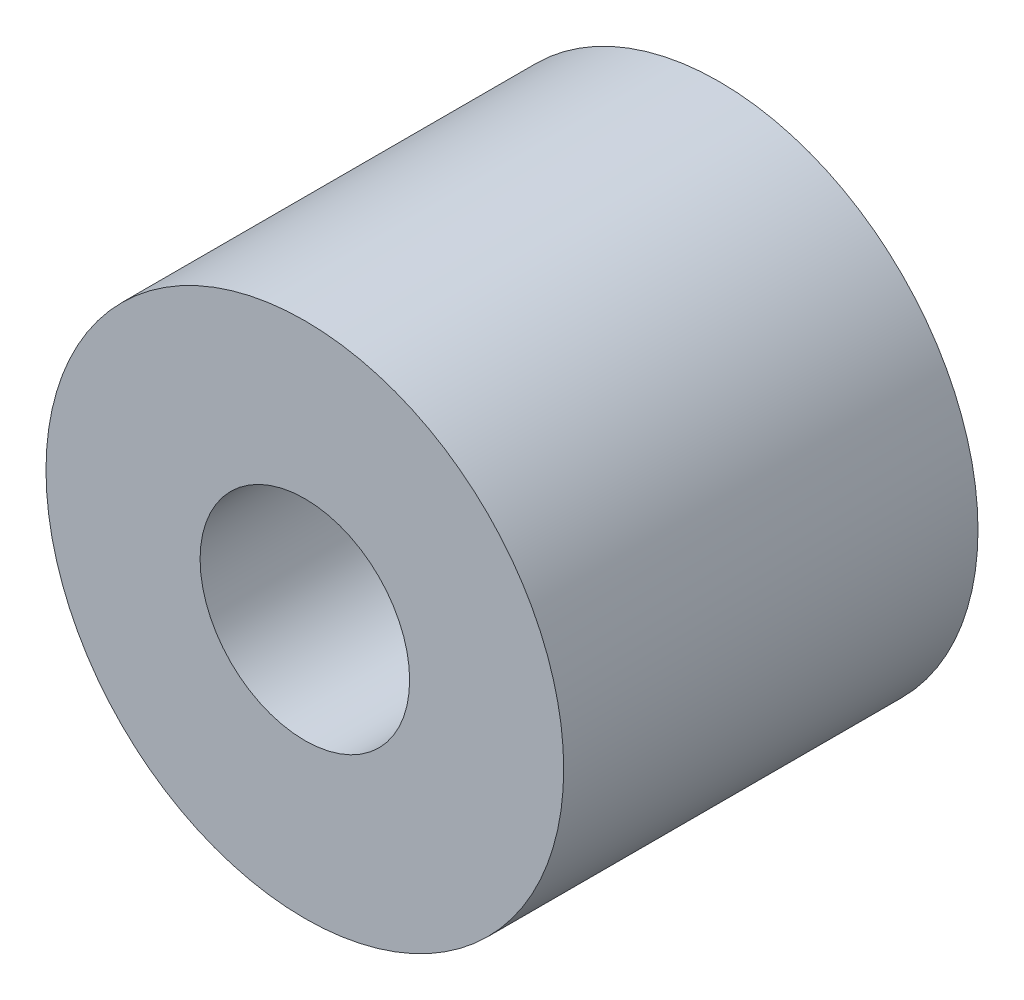
SolidWorks part; units mm, degrees
ref_plane "Front Plane" through (0, 0, 0) normal (0, 0, 1) x (1, 0, 0)
ref_plane "Top Plane" through (0, 0, 0) normal (0, 1, 0) x (1, 0, 0)
ref_plane "Right Plane" through (0, 0, 0) normal (1, 0, 0) x (0, 0, -1)
sketch "Sketch1" plane through (0, 0, 0) normal (0, 1, 0) x (1, 0, 0)
  line L0 (2.125, -3.75) -> (5.25, -3.75)
  line L1 (5.25, -3.75) -> (5.25, 0)
  line L2 (5.25, 0) -> (2.125, 0)
  line L3 (2.125, 0) -> (2.125, -3.75)
  line L4 (0, 0) -> (0, -3.75) construction
  dimension "D1" = 2.125
  dimension "D2" = 5.25
  dimension "D3" = 3.75
revolve "Revolve1" add sketch "Sketch1" angle 360 about L4 reverse direction yes
sketch "Sketch2" plane through (0, 0, 3.75) normal (0, 0, 1) x (1, 0, 0)
  circle A0 centre (0, 0) radius 2.125
  circle A1 centre (0, 0) radius 5.25
  dimension "D1" = 4.25
  dimension "D2" = 10.5
extrude "Boss-Extrude1" add sketch "Sketch2" along normal blind 4.6524
